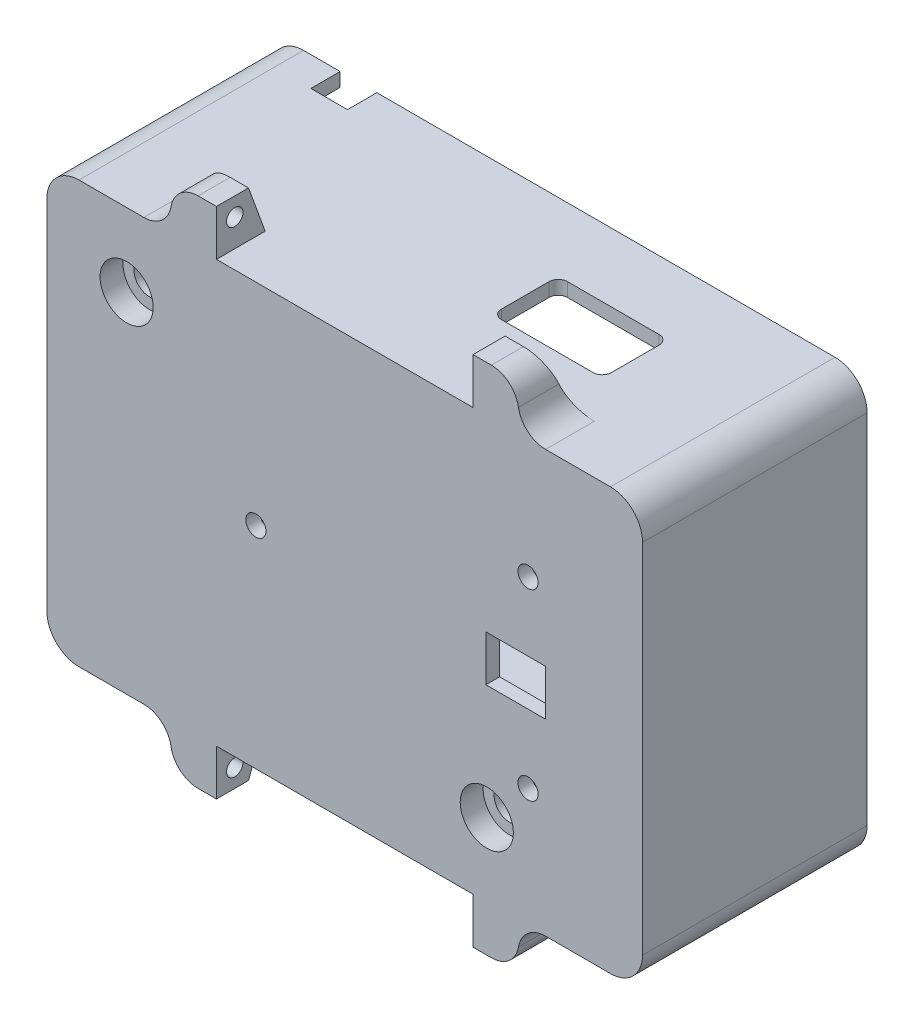
SolidWorks part; units mm, degrees
ref_plane "Front Plane" through (0, 0, 0) normal (0, 0, 1) x (1, 0, 0)
ref_plane "Top Plane" through (0, 0, 0) normal (0, 1, 0) x (1, 0, 0)
ref_plane "Right Plane" through (0, 0, 0) normal (1, 0, 0) x (0, 0, -1)
sketch "Sketch1" plane through (0, 0, 0) normal (0, 0, 1) x (1, 0, 0)
  line L0 (29.7, 10) -> (29.7, -10) construction
  line L1 (25.1, 2.5) -> (31.6, 2.5)
  line L2 (25.1, 2.5) -> (25.1, -2.5)
  line L3 (25.1, -2.5) -> (31.6, -2.5)
  line L4 (31.6, 2.5) -> (31.6, -2.5)
  line L6 (-20.3, 20.5) -> (31.7, 20.5) construction
  line L7 (-20.3, 20.5) -> (-20.3, -20.5) construction
  line L8 (-20.3, -20.5) -> (31.7, -20.5) construction
  line L9 (31.7, 20.5) -> (31.7, -20.5) construction
  line L10 (21.0461, -10) -> (39.7, -10) construction
  line L11 (21.0461, -10) -> (21.0461, 10) construction
  line L12 (21.0461, 10) -> (39.7, 10) construction
  line L13 (39.7, -10) -> (39.7, 10) construction
  line L14 (-19.3, -23) -> (38.7, -23)
  line L15 (-22.8, -19.5) -> (-22.8, 19.5)
  line L16 (-19.3, 23) -> (38.7, 23)
  line L17 (42.2, -19.5) -> (42.2, 19.5)
  circle A0 centre (0, 0) radius 1.1
  circle A1 centre (29.7, 10) radius 1.1
  circle A2 centre (29.7, -10) radius 1.1
  circle A3 centre (-14.1, 15) radius 2.9
  circle A4 centre (25.2, -15) radius 2.9
  arc A5 (38.7, 23) -> (42.2, 19.5) centre (38.7, 19.5) cw
  arc A6 (-22.8, 19.5) -> (-19.3, 23) centre (-19.3, 19.5) cw
  arc A7 (-19.3, -23) -> (-22.8, -19.5) centre (-19.3, -19.5) cw
  arc A8 (38.7, -23) -> (42.2, -19.5) centre (38.7, -19.5) ccw
  point P11 (29.7, 0)
  point P13 (31.6, 0)
  point P21 (-20.3, 0)
  point P22 (39.7, 0)
  point P35 (-22.8, 23)
  point P38 (-22.8, -23)
  point P41 (42.2, -23)
  dimension "D1" = 2.2
  dimension "D10" = 5.8
  dimension "D23" = 3.5
  dimension "D2" = 20
  dimension "D3" = 29.7
  dimension "D4" = 5
  dimension "D5" = 6.5
  dimension "D6" = 1.9
  dimension "D7" = 41
  dimension "D8" = 52
  dimension "D9" = 5.5
  dimension "D11" = 6.5
  dimension "D12" = 2
  dimension "D13" = 5.5
  dimension "D14" = 6.2
  dimension "D15" = 20
  dimension "D16" = 10
  dimension "D17" = 2.5
  dimension "D18" = 2.5
  dimension "D19" = 2.5
  dimension "D20" = 2.5
  dimension "D21" = 46
  dimension "D22" = 65
extrude "Boss-Extrude1" add sketch "Sketch1" along normal blind 1.5
sketch "Sketch2" plane through (0, 0, 0) normal (0, 0, -1) x (-1, 0, 0)
  line L0 (-31.7, 20.5) -> (-31.7, -20.5) construction
  line L1 (20.3, 20.5) -> (-31.7, 20.5) construction
  line L2 (20.3, 20.5) -> (20.3, -20.5) construction
  line L3 (20.3, -20.5) -> (-31.7, -20.5) construction
  line L4 (-31.7, 20.5) -> (-31.7, -20.5) construction
  line L5 (20.3, 20.5) -> (-31.7, 20.5) construction
  line L6 (20.3, 20.5) -> (20.3, -20.5) construction
  line L7 (20.3, -20.5) -> (-31.7, -20.5) construction
  line L8 (-21.0461, 10) -> (-39.7, 10) construction
  line L9 (-39.7, -10) -> (-39.7, 10) construction
  line L10 (-21.0461, -10) -> (-39.7, -10) construction
  line L11 (-21.0461, 10) -> (-39.7, 10) construction
  line L12 (-39.7, -10) -> (-39.7, 10) construction
  line L13 (-21.0461, -10) -> (-39.7, -10) construction
  circle A0 centre (-29.7, -10) radius 1.1 construction
  circle A1 centre (-29.7, 10) radius 1.1 construction
  circle A2 centre (14.1, 15) radius 2.9 construction
  circle A3 centre (0, 0) radius 1.1 construction
  circle A4 centre (-25.2, -15) radius 2.9 construction
  circle A5 centre (-29.7, -10) radius 1.1 construction
  circle A6 centre (-29.7, 10) radius 1.1 construction
  circle A7 centre (14.1, 15) radius 2.9
  circle A8 centre (0, 0) radius 1.1 construction
  circle A9 centre (-25.2, -15) radius 2.9
  circle A10 centre (-25.2, -15) radius 4.4
  circle A11 centre (14.1, 15) radius 4.4
  dimension "D1" = 1.5
  dimension "D2" = 1.5
extrude "Boss-Extrude2" add sketch "Sketch2" along normal blind 1
sketch "Sketch4" plane through (0, 0, -1) normal (0, 0, -1) x (-1, 0, 0)
  circle A0 centre (-25.2, -15) radius 1.7
  circle A1 centre (14.1, 15) radius 1.7
  circle A2 centre (14.1, 15) radius 2.9 construction
  circle A3 centre (-25.2, -15) radius 2.9 construction
  circle A4 centre (14.1, 15) radius 4.4 construction
  circle A5 centre (14.1, 15) radius 4.4
  circle A6 centre (-25.2, -15) radius 4.4 construction
  circle A7 centre (-25.2, -15) radius 4.4
  dimension "D1" = 3.4
extrude "Boss-Extrude3" add sketch "Sketch4" along normal blind 5.2
sketch "Sketch5" plane through (0, 0, 0) normal (0, 0, -1) x (-1, 0, 0)
  line L4 (-40.7, 19.5) -> (-40.7, -19.5)
  line L5 (-38.7, -21.5) -> (19.3, -21.5)
  line L6 (21.3, -19.5) -> (21.3, 19.5)
  line L7 (19.3, 21.5) -> (-38.7, 21.5)
  line L8 (-42.2, 19.5) -> (-42.2, -19.5)
  line L9 (-38.7, -23) -> (19.3, -23)
  line L10 (22.8, -19.5) -> (22.8, 19.5)
  line L11 (19.3, 23) -> (-38.7, 23)
  line L12 (-42.2, 19.5) -> (-42.2, -19.5)
  line L13 (-38.7, -23) -> (19.3, -23)
  line L14 (22.8, -19.5) -> (22.8, 19.5)
  line L15 (19.3, 23) -> (-38.7, 23)
  arc A5 (-38.7, 21.5) -> (-40.7, 19.5) centre (-38.7, 19.5) ccw
  arc A6 (-40.7, -19.5) -> (-38.7, -21.5) centre (-38.7, -19.5) ccw
  arc A7 (19.3, -21.5) -> (21.3, -19.5) centre (19.3, -19.5) ccw
  arc A8 (21.3, 19.5) -> (19.3, 21.5) centre (19.3, 19.5) ccw
  arc A9 (-38.7, 23) -> (-42.2, 19.5) centre (-38.7, 19.5) ccw
  arc A10 (-42.2, -19.5) -> (-38.7, -23) centre (-38.7, -19.5) ccw
  arc A11 (19.3, -23) -> (22.8, -19.5) centre (19.3, -19.5) ccw
  arc A12 (22.8, 19.5) -> (19.3, 23) centre (19.3, 19.5) ccw
  arc A13 (-38.7, 23) -> (-42.2, 19.5) centre (-38.7, 19.5) ccw
  arc A14 (-42.2, -19.5) -> (-38.7, -23) centre (-38.7, -19.5) ccw
  arc A15 (19.3, -23) -> (22.8, -19.5) centre (19.3, -19.5) ccw
  arc A16 (22.8, 19.5) -> (19.3, 23) centre (19.3, 19.5) ccw
  dimension "D1" = 0
  dimension "D2" = 1.5
extrude "Boss-Extrude4" add sketch "Sketch5" along normal blind 23
sketch "Sketch6" plane through (0, 0, 1.5) normal (0, 0, 1) x (1, 0, 0)
  line L0 (-4.3, 23) -> (-4.3, 28)
  line L1 (38.7, 23) -> (-19.3, 23) construction
  line L2 (23.7, 23) -> (23.7, 28)
  line L3 (-4.3, 23) -> (23.7, 23) construction
  line L4 (-19.3, -23) -> (38.7, -23) construction
  line L5 (23.7, 28) -> (28.7, 28)
  line L6 (-4.3, 28) -> (-9.3, 28)
  line L7 (28.7, 28) -> (28.7, 23)
  line L8 (-9.3, 28) -> (-9.3, 23)
  line L9 (-9.3, 23) -> (-4.3, 23)
  line L10 (28.7, 23) -> (23.7, 23)
  line L11 (42.2, 0) -> (34.6391, 0) construction
  line L12 (42.2, -19.5) -> (42.2, 19.5) construction
  line L13 (-4.3, -23) -> (23.7, -23) construction
  line L14 (28.7, -23) -> (23.7, -23)
  line L15 (-9.3, -23) -> (-4.3, -23)
  line L16 (-9.3, -28) -> (-9.3, -23)
  line L17 (28.7, -28) -> (28.7, -23)
  line L18 (-4.3, -28) -> (-9.3, -28)
  line L19 (23.7, -28) -> (28.7, -28)
  line L20 (23.7, -23) -> (23.7, -28)
  line L21 (-4.3, -23) -> (-4.3, -28)
  point P6 (9.7, 23)
  point P9 (9.7, -23)
  dimension "D1" = 28
  dimension "D2" = 5
  dimension "D3" = 5
  dimension "D4" = 5
extrude "Boss-Extrude5" add sketch "Sketch6" against normal blind 3.5
fillet "Fillet1" radius 3 4 edges at (-9.3, -28, -0.25) (28.7, -28, -0.25) (28.7, 28, -0.25) (-9.3, 28, -0.25)
fillet "Fillet2" radius 3 4 edges at (-9.3, -23, -0.25) (28.7, -23, -0.25) (28.7, 23, -0.25) (-9.3, 23, -0.25)
chamfer "Chamfer1" distance 5 angle 20 4 edges at (-8.258, 23, -2) (27.658, 23, -2) (-8.258, -23, -2) (27.658, -23, -2) first distance on face at (-7.2748, 25.5, -2) first distance on face at (26.6748, 25.5, -2) first distance on face at (-7.2748, -25.5, -2) first distance on face at (26.6748, -25.5, -2)
sketch "Sketch7" plane through (0, 23, 0) normal (0, 1, 0) x (1, 0, 0)
  line L0 (29.6, 6.2) -> (20.8, 6.2) construction
  line L1 (26.2, 13.7) -> (17.7, 13.7) construction
  line L2 (26.2, 13.7) -> (26.2, 10.2) construction
  line L3 (26.2, 10.2) -> (17.7, 10.2) construction
  line L4 (17.7, 13.7) -> (17.7, 10.2) construction
  line L7 (16.95, 15.55) -> (26.95, 15.55)
  line L8 (15.95, 14.55) -> (15.95, 9.35)
  line L9 (16.95, 8.35) -> (26.95, 8.35)
  line L10 (27.95, 14.55) -> (27.95, 9.35)
  arc A0 (15.95, 9.35) -> (16.95, 8.35) centre (16.95, 9.35) ccw
  arc A1 (26.95, 8.35) -> (27.95, 9.35) centre (26.95, 9.35) ccw
  arc A2 (26.95, 15.55) -> (27.95, 14.55) centre (26.95, 14.55) cw
  arc A3 (16.95, 15.55) -> (15.95, 14.55) centre (16.95, 14.55) ccw
  point P11 (29.9361, 6.4781)
  point P12 (27.95, 11.95)
  point P13 (26.2, 11.95)
  point P14 (21.95, 15.55)
  point P15 (21.95, 13.7)
  point P20 (27.95, 8.35)
  point P23 (27.95, 15.55)
  point P26 (15.95, 15.55)
  dimension "D7" = 1
  dimension "D1" = 7.5
  dimension "D2" = 14
  dimension "D3" = 8.5
  dimension "D4" = 3.5
  dimension "D5" = 12
  dimension "D6" = 7.2
extrude "Cut-Extrude1" cut sketch "Sketch7" against normal blind 3.5
sketch "Sketch8" plane through (23.7, 0, 0) normal (-1, 0, 0) x (0, 0, 1)
  line L0 (-2, 28) -> (1.5, 28) construction
  line L1 (1.5, 28) -> (1.5, 23) construction
  line L2 (-6.7786, 0) -> (6.7786, 0) construction
  circle A0 centre (-0.5, 26) radius 0.9
  circle A1 centre (-0.5, -26) radius 0.9
  point P11 (0, 0)
  dimension "D2" = 1.8
  dimension "D1" = 2
  dimension "D3" = 2
extrude "Cut-Extrude2" cut sketch "Sketch8" against normal blind 1.5 and the other way blind 29.5
sketch "Sketch10" plane through (0, 21.5, 0) normal (0, -1, 0) x (1, 0, 0)
  line L0 (-19.3, -23) -> (38.7, -23) construction
  line L1 (-17.8, -23) -> (-8.8, -23)
  line L2 (-17.8, -23) -> (-17.8, -18.8)
  line L3 (-17.8, -18.8) -> (-8.8, -18.8)
  line L4 (-8.8, -23) -> (-8.8, -18.8)
  line L5 (-19.3, -23) -> (-19.3, -17.3)
  line L6 (-19.3, -17.3) -> (-7.3, -17.3)
  line L7 (-7.3, -23) -> (-7.3, -17.3)
  line L8 (-19.3, -23) -> (-17.8, -23)
  line L9 (-8.8, -23) -> (-7.3, -23)
  line M15 (-19.3, -23) -> (38.7, -23)
  dimension "D1" = 4.2
  dimension "D2" = 9
  dimension "D3" = 3.5
  dimension "D4" = 1.5
extrude "Boss-Extrude6" add sketch "Sketch10" along normal blind 4.2 contours L7 L6 L5 L2 L3 L4 M15 region at (-18.55, 21.5, -22.8672)
sketch "Sketch12" plane through (0, 17.3, 0) normal (0, -1, 0) x (1, 0, 0)
  line L0 (-19.3, -17.3) -> (-7.3, -17.3) construction
  line L1 (-19.3, -23) -> (-14.3, -23)
  line L2 (-19.3, -23) -> (-19.3, -17.3)
  line L3 (-19.3, -17.3) -> (-14.3, -17.3)
  line L4 (-14.3, -23) -> (-14.3, -17.3)
  line L5 (-17.8, -18.8) -> (-8.8, -18.8) construction
  line L6 (-7.3, -23) -> (-9.8, -23)
  line L7 (-7.3, -23) -> (-7.3, -17.3)
  line L8 (-7.3, -17.3) -> (-9.8, -17.3)
  line L9 (-9.8, -23) -> (-9.8, -17.3)
  line L10 (-9.8, -17.3) -> (-14.3, -17.3)
  line L11 (-9.8, -17.3) -> (-9.8, -18.8)
  line L12 (-9.8, -18.8) -> (-14.3, -18.8)
  line L13 (-14.3, -17.3) -> (-14.3, -18.8)
  line M5 (-8.8, -23) -> (-7.3, -23)
  line M6 (-7.3, -23) -> (-7.3, -17.3)
  line M7 (-7.3, -17.3) -> (-19.3, -17.3)
  line M8 (-19.3, -17.3) -> (-19.3, -23)
  line M9 (-19.3, -23) -> (-17.8, -23)
  line M10 (-17.8, -23) -> (-17.8, -18.8)
  line M11 (-17.8, -18.8) -> (-8.8, -18.8)
  line M12 (-8.8, -18.8) -> (-8.8, -23)
  dimension "D1" = 5
  dimension "D2" = 2.5
extrude "Boss-Extrude7" add sketch "Sketch12" along normal blind 1.5 contours L1 L4 M11 M10 | L4 M11 M7 M8 M9 M10 | L9 L4 M11 M7 | L9 M11 M12 M5 M6 M7 | L9 L6 M12 M11 region at (-19.2242, 17.3, -20.15) region at (-16.05, 17.3, -20.9) region at (-12.05, 17.3, -18.05) region at (-8.2366, 17.3, -19.8366) region at (-9.3, 17.3, -20.9)
sketch "Sketch14" plane through (0, 21.5, 0) normal (0, -1, 0) x (1, 0, 0)
  line L0 (-8.8, -23) -> (-8.8, -18.8) construction
  line L1 (-15.3, -22) -> (-11.3, -22)
  line L2 (-15.3, -22) -> (-15.3, -19.8)
  line L3 (-15.3, -19.8) -> (-11.3, -19.8)
  line L4 (-11.3, -22) -> (-11.3, -19.8)
  line L5 (-8.8, -23) -> (-8.8, -18.8) construction
  line L6 (-17.8, -18.8) -> (-8.8, -18.8) construction
  line L7 (-17.8, -18.8) -> (-8.8, -18.8) construction
  line L8 (-17.8, -23) -> (-8.8, -23) construction
  line L9 (-15.3, -22) -> (-11.3, -22)
  line L10 (-15.3, -22) -> (-15.3, -23)
  line L11 (-15.3, -23) -> (-11.3, -23)
  line L12 (-11.3, -22) -> (-11.3, -23)
  point P6 (-8.8, -20.9)
  point P7 (-11.3, -20.9)
  point P10 (-13.3, -19.8)
  point P11 (-13.3, -18.8)
  point P17 (-3.8995, -20.2)
  line M8 (-17.8, -23) -> (-8.8, -23)
  dimension "D1" = 4
  dimension "D2" = 2.2
extrude "Cut-Extrude4" cut sketch "Sketch14" against normal blind 1.5 contours L1 L4 L3 L2 | L12 L1 L10 M8 region at (-13.3, 21.5, -20.9) region at (-13.3, 21.5, -22.5)
sketch "Sketch15" plane through (0, 0, -23) normal (0, 0, -1) x (-1, 0, 0)
  line L0 (22.8, -19.5) -> (22.8, -18)
  line L1 (22.8, -19.5) -> (22.8, 19.5) construction
  line L2 (22.8, -18) -> (17.8, -18)
  line L3 (17.8, -18) -> (17.8, -23)
  line L4 (-38.7, -23) -> (19.3, -23) construction
  line L5 (17.8, -23) -> (19.3, -23)
  line L6 (-9.7, -21.5) -> (-9.7, 21.5) construction
  line L7 (-38.7, -21.5) -> (19.3, -21.5) construction
  line L8 (7.3, 21.5) -> (-38.7, 21.5) construction
  line L10 (-37.2, -18) -> (-37.2, -23)
  line L11 (-37.2, -23) -> (-38.7, -23)
  line L12 (-42.2, -19.5) -> (-42.2, -18)
  line L13 (-42.2, -18) -> (-37.2, -18)
  line L14 (-3.4706, 0) -> (-15.9294, 0) construction
  line L15 (-42.2, 18) -> (-37.2, 18)
  line L16 (-42.2, 19.5) -> (-42.2, 18)
  line L17 (-37.2, 23) -> (-38.7, 23)
  line L18 (-37.2, 18) -> (-37.2, 23)
  line L19 (17.8, 23) -> (19.3, 23)
  line L20 (17.8, 18) -> (17.8, 23)
  line L21 (22.8, 18) -> (17.8, 18)
  line L22 (22.8, 19.5) -> (22.8, 18)
  circle A0 centre (20, -20.2) radius 1.1
  arc A1 (19.3, -23) -> (22.8, -19.5) centre (19.3, -19.5) ccw construction
  arc A2 (19.3, -23) -> (22.8, -19.5) centre (19.3, -19.5) ccw
  circle A3 centre (-39.4, -20.2) radius 1.1
  arc A4 (-38.7, -23) -> (-42.2, -19.5) centre (-38.7, -19.5) cw
  arc A5 (-38.7, 23) -> (-42.2, 19.5) centre (-38.7, 19.5) ccw
  circle A6 centre (-39.4, 20.2) radius 1.1
  arc A7 (19.3, 23) -> (22.8, 19.5) centre (19.3, 19.5) cw
  circle A8 centre (20, 20.2) radius 1.1
  point P30 (-9.7, 0)
  dimension "D2" = 2.2
  dimension "D1" = 5
  dimension "D3" = 2.2
  dimension "D4" = 2.2
extrude "Boss-Extrude9" add sketch "Sketch15" against normal blind 5
fillet "Fillet3" radius 1.7 3 edges at (37.2, 18, -20.5) (-17.8, -18, -20.5) (37.2, -18, -20.5)
sketch "Sketch16" plane through (0, 0, -23) normal (0, 0, -1) x (-1, 0, 0)
  circle A0 centre (-39.4, -20.2) radius 1.1
  circle A1 centre (20, -20.2) radius 1.1
  circle A2 centre (20, 20.2) radius 1.1
  circle A3 centre (20, 20.2) radius 1.1 construction
  circle A4 centre (-39.4, 20.2) radius 1.1
  circle A5 centre (-39.4, 20.2) radius 1.1 construction
extrude "Cut-Extrude5" cut sketch "Sketch16" against normal blind 5
chamfer "Chamfer2" distance 6.4 angle 25 1 edges at (-13.3, 21.5, -17.3) first distance on face at (-13.3, 18.65, -17.3)
